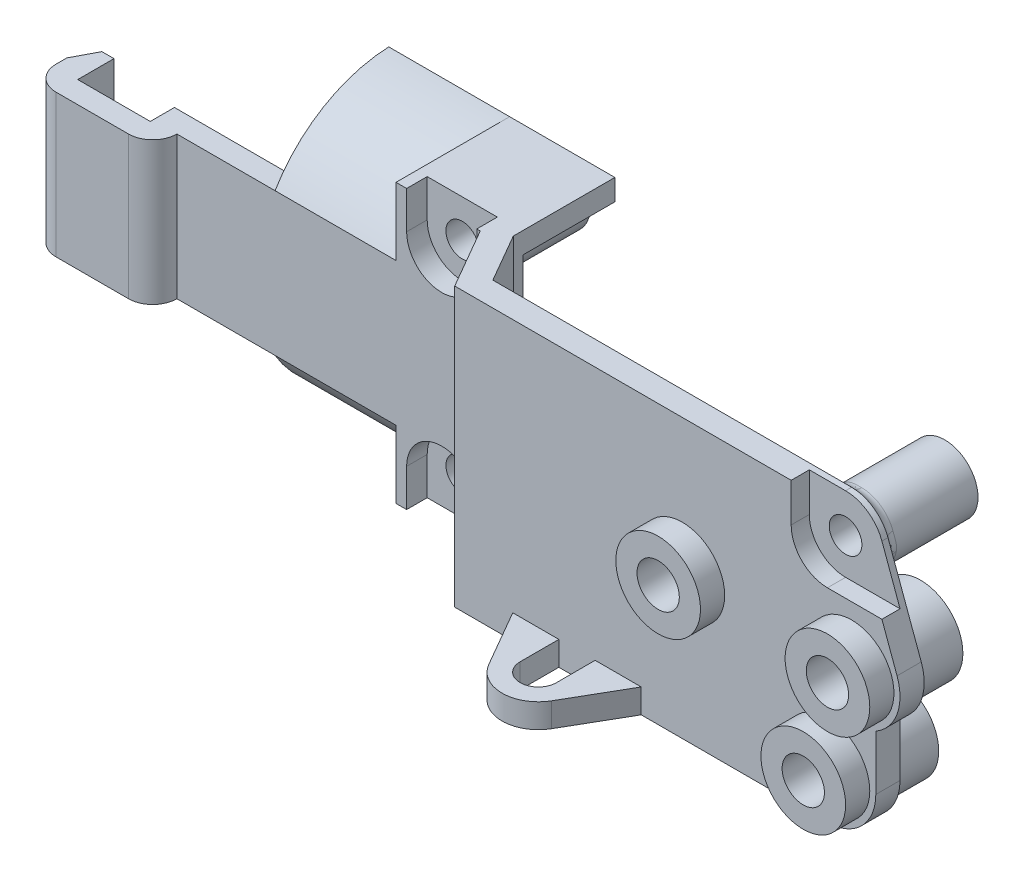
SolidWorks part; units mm, degrees
ref_plane "Front Plane" through (0, 0, 0) normal (0, 0, 1) x (1, 0, 0)
ref_plane "Top Plane" through (0, 0, 0) normal (0, 1, 0) x (1, 0, 0)
ref_plane "Right Plane" through (0, 0, 0) normal (1, 0, 0) x (0, 0, -1)
sketch "Sketch1" plane through (0, 0, 0) normal (0, 0, 1) x (1, 0, 0)
  line L0 (-4.567, -11.8) -> (25.103, -11.8)
  line L1 (29.103, -7.8) -> (29.103, -3.2641)
  line L2 (28.1084, 9.0988) -> (30.8598, 1.5735)
  line L3 (25.103, 11.2) -> (-4.567, 11.2)
  line L4 (29.103, -7.8) -> (29.103, -3.2641) construction
  line L9 (999.5524, 0.2) -> (-4.567, 0.2) construction
  line L10 (-4.567, 11.2) -> (-4.567, -11.8)
  arc A0 (29.103, -3.2641) -> (30.8598, 1.5735) centre (27.103, 0.2) ccw
  circle A2 centre (-0.897, 0.2) radius 1.5
  circle A3 centre (13.103, 0.2) radius 1.75
  circle A4 centre (27.103, 0.2) radius 1.75
  circle A5 centre (25.103, -7.8) radius 1.75
  arc A6 (25.103, -11.8) -> (29.103, -7.8) centre (25.103, -7.8) ccw
  circle A7 centre (25.103, 8) radius 1.35
  arc A9 (25.103, 11.2) -> (28.1084, 9.0988) centre (25.103, 8) cw
  circle A12 centre (-0.897, 0.2) radius 1.5 construction
  point P0 (31.103, 0.2)
  dimension "D9" = 3.5
  dimension "D10" = 3.5
  dimension "D11" = 3
  dimension "D12" = 3.5
  dimension "D13" = 2.7
  dimension "D14" = 4
  dimension "D15" = 3.2
  dimension "D19" = 4
  dimension "D3" = 35.67
  dimension "D4" = 14
  dimension "D7" = 12
  dimension "D8" = 2
  dimension "D18" = 23
  dimension "D20" = 8
  dimension "D21" = 7.8
extrude "Boss-Extrude1" add sketch "Sketch1" along normal blind 2 contours L10 L0 A6 L1 A0 L2 A9 L3 | A3 | A7 | A4 | A5
ref_plane "Plane1" through (0, -0.3, 0) normal (0, 1, 0) x (-1, 0, 0)
sketch "Sketch4" plane through (0, 0, 0) normal (0, 0, 1) x (1, 0, 0)
  circle A0 centre (27.103, 0.2) radius 3.5
  circle A1 centre (27.103, 0.2) radius 1.75 construction
  circle A2 centre (27.103, 0.2) radius 1.75
  circle A3 centre (25.103, -7.8) radius 1.75 construction
  circle A4 centre (25.103, -7.8) radius 1.75
  circle A5 centre (25.103, -7.8) radius 3.5
  dimension "D1" = 7
extrude "Boss-Extrude3" add sketch "Sketch4" against normal offset from surface (3.7 mm away) 3.7 up to face at (28.853, 0.2, 0) offset beyond the face yes
sketch "Sketch3" plane through (0, 0, 2) normal (0, 0, -1) x (-1, 0, 0)
  circle A0 centre (-25.103, -7.8) radius 3.5
  circle A1 centre (-25.103, -7.8) radius 1.75 construction
  circle A2 centre (-25.103, -7.8) radius 1.75
  circle A3 centre (-27.103, 0.2) radius 1.75 construction
  circle A4 centre (-13.103, 0.2) radius 1.75 construction
  circle A5 centre (-27.103, 0.2) radius 1.75
  circle A6 centre (-13.103, 0.2) radius 1.75
  circle A7 centre (-27.103, 0.2) radius 3.5
  circle A8 centre (-13.103, 0.2) radius 3.5
  dimension "D1" = 7
extrude "Boss-Extrude4" add sketch "Sketch3" against normal offset from surface (2 mm away) 7.7 up to face at (30.603, 0.2, -3.7)
sketch "Sketch5" plane through (0, -0.3, 0) normal (0, 1, 0) x (1, 0, 0)
  line L0 (-4.567, -2) -> (-4.567, 0) construction
  line L8 (29.9414, -1) -> (13.8394, -1) construction
  line L17 (25.103, 0) -> (-4.567, 0) construction
  line L18 (25.103, -2) -> (-4.567, -2) construction
  line L19 (-5.7217, -2) -> (-8.6085, 3)
  line L20 (-6.8764, 4) -> (-4.567, 0)
  line L21 (-4.567, 0) -> (-4.567, -2)
  line L22 (-4.567, -2) -> (-5.7217, -2)
  line L23 (-33.697, 3) -> (-8.6085, 3)
  line L24 (-33.697, 1) -> (-33.697, 3)
  line L25 (-43.697, 1) -> (-33.697, 1)
  line L26 (-43.697, 3.9) -> (-43.697, 1)
  line L27 (-42.697, 5.8) -> (-43.697, 3.9)
  line L28 (-41.697, 5.8) -> (-42.697, 5.8)
  line L29 (-41.697, 2.8) -> (-41.697, 5.8)
  line L30 (-35.697, 2.8) -> (-41.697, 2.8)
  line L31 (-35.697, 4.8) -> (-35.697, 2.8)
  line L32 (-6.8764, 4.8) -> (-35.697, 4.8)
  line L33 (-6.8764, 4.8) -> (-6.8764, 4)
  dimension "D1" = 120
  dimension "D2" = 1.8
  dimension "D3" = 1.9
  dimension "D4" = 1
  dimension "D5" = 1.8
  dimension "D6" = 5
  dimension "D7" = 2
  dimension "D8" = 2
  dimension "D9" = 1
  dimension "D10" = 2
  dimension "D11" = 2
  dimension "D12" = 8
  dimension "D13" = 1
  dimension "D14" = 34.8
extrude "Boss-Extrude5" add sketch "Sketch5" along normal mid plane 11.8
fillet "Fillet1" radius 2 2 edges at (-43.697, -0.3, -1) (-33.697, -0.3, -1)
sketch "Sketch6" plane through (0, 0, 0) normal (0, 0, 1) x (1, 0, 0)
  circle A0 centre (25.103, 8) radius 1.35 construction
  circle A1 centre (25.103, 8) radius 1.35
  circle A2 centre (25.103, 8) radius 2.75
  dimension "D1" = 5.5
extrude "Boss-Extrude6" add sketch "Sketch6" against normal blind 7.7
sketch "Sketch8" plane through (0, 0, 0) normal (0, 0, 1) x (1, 0, 0)
  circle A0 centre (-0.897, 0.2) radius 3
  circle A1 centre (-0.897, 0.2) radius 1.5 construction
  circle A2 centre (-0.897, 0.2) radius 1.5
  dimension "D1" = 6
extrude "Boss-Extrude7" add sketch "Sketch8" against normal blind 2.65
sketch "Sketch9" plane through (0, -0.3, 0) normal (0, -1, 0) x (1, 0, 0)
  line L5 (-8.6085, -3) -> (-5.7217, 2) construction
  line L6 (-4.567, 0) -> (-6.8764, -4) construction
  line L7 (-6.8764, -4.8) -> (-35.697, -4.8) construction
  line L8 (-6.8764, -4) -> (-6.8764, -4.8) construction
  line L13 (-1.123, 1) -> (4.8741, 1) construction
  line L14 (-4.567, 0) -> (25.103, 0) construction
  line L15 (-4.567, 2) -> (25.103, 2) construction
  line L16 (-8.6085, -4.8) -> (-6.8764, -4.8)
  line L17 (-8.6085, -3) -> (-8.6085, -4.8)
  line L18 (-6.8764, -4.8) -> (-6.8764, -4)
  line L19 (-4.567, 0) -> (-4.567, 2)
  line L20 (-6.8764, -4) -> (-4.567, 0)
  line L21 (-4.567, 2) -> (-5.7217, 2)
  line L22 (-5.7217, 2) -> (-8.6085, -3)
extrude "Boss-Extrude10" add sketch "Sketch9" along normal mid plane 23
sketch "Sketch10" plane through (0, 0, -3) normal (0, 0, -1) x (-1, 0, 0)
  line L0 (25.5764, -11.8) -> (6.8764, -11.8)
  line L1 (6.8764, -11.8) -> (6.8764, -10.05)
  line L2 (6.8764, -10.05) -> (9.2304, -10.05)
  line L3 (12.9925, -6.0579) -> (14.597, -4.6025)
  line L4 (14.597, -4.6025) -> (14.597, 4.0025)
  line L5 (16.397, 4.8) -> (16.397, -5.4)
  line L6 (16.397, -5.4) -> (14.3251, -7.2792)
  line L7 (14.0708, -10.5) -> (25.5764, -10.5)
  line L8 (25.5764, -10.5) -> (25.5764, -11.8)
  line L9 (25.5764, 9.9) -> (25.5764, 11.2)
  line L10 (14.0708, 9.9) -> (25.5764, 9.9)
  line L11 (16.397, 4.8) -> (14.3251, 6.6792)
  line L12 (-8.6455, -0.3) -> (-5.3863, -0.3) construction
  line L13 (-25.103, 11.2) -> (5.7217, 11.2) construction
  line L14 (12.9925, 5.4579) -> (14.597, 4.0025)
  line L15 (6.8764, 9.45) -> (9.2304, 9.45)
  line L16 (6.8764, 11.2) -> (6.8764, 9.45)
  line L17 (25.5764, 11.2) -> (6.8764, 11.2)
  line L18 (6.8764, 11.2) -> (6.8764, -11.8) construction
  line L19 (6.8764, 11.2) -> (6.8764, -11.8) construction
  line L22 (5.7217, -11.8) -> (-25.103, -11.8) construction
  line L25 (16.397, 4.8) -> (16.397, 2.7) construction
  line L26 (-25.103, 11.2) -> (4.567, 11.2) construction
  arc A0 (9.2304, -10.05) -> (12.9925, -6.0579) centre (11.797, -8.7) cw
  arc A1 (14.3251, -7.2792) -> (14.0708, -10.5) centre (11.797, -8.7) cw
  arc A2 (14.3251, 6.6792) -> (14.0708, 9.9) centre (11.797, 8.1) ccw
  arc A3 (9.2304, 9.45) -> (12.9925, 5.4579) centre (11.797, 8.1) ccw
  circle A4 centre (11.797, 8.1) radius 1.35
  circle A5 centre (11.797, -8.7) radius 1.35
  dimension "D1" = 2.9
  dimension "D14" = 2.7
  dimension "D11" = 10.9
  dimension "D2" = 1.3
  dimension "D3" = 1.8
  dimension "D4" = 18.7
  dimension "D5" = 1.8
  dimension "D6" = 10.2
  dimension "D7" = 1.3
  dimension "D8" = 1.75
  dimension "D9" = 3.1
  dimension "D10" = 3.1
  dimension "D12" = 1.8
extrude "Boss-Extrude11" add sketch "Sketch10" along normal offset from surface (9.4 mm away) 9.4 up to face at (-21.1527, -0.3, -3)
sketch "Sketch11" plane through (0, 0, -3) normal (0, 0, -1) x (-1, 0, 0)
  line L0 (25.5764, 11.2) -> (8.6085, 11.2) construction
  line L1 (8.6085, -11.8) -> (17.0924, -11.8)
  line L2 (8.6085, -11.8) -> (8.6085, 11.2)
  line L3 (8.6085, 11.2) -> (17.0924, 11.2)
  line L4 (17.0924, -11.8) -> (17.0924, 11.2)
  line L6 (8.6085, 5.6) -> (8.6085, -6.2) construction
  line L7 (8.6085, -11.8) -> (25.5764, -11.8) construction
  circle A0 centre (11.797, 8.1) radius 1.35 construction
  circle A1 centre (11.797, -8.7) radius 1.35 construction
  circle A2 centre (11.797, 8.1) radius 1.35
  circle A3 centre (11.797, -8.7) radius 1.35
extrude "Boss-Extrude12" add sketch "Sketch11" along normal up to surface (1.8 mm away) up to face at (-10.3321, -0.3, -4.8)
sketch "Sketch13" plane through (0, 0, 2) normal (0, 0, -1) x (-1, 0, 0)
  line L0 (-29.607, 5) -> (-25.103, 5)
  line L1 (-28.1084, 9.0988) -> (-30.8598, 1.5735) construction
  line L2 (-22.103, 8) -> (-22.103, 11.2)
  line L3 (-25.103, 11.2) -> (4.567, 11.2) construction
  line L4 (-28.1084, 9.0988) -> (-29.607, 5)
  line L5 (-25.103, 11.2) -> (-22.103, 11.2)
  arc A0 (-25.103, 5) -> (-22.103, 8) centre (-25.103, 8) ccw
  circle A1 centre (-25.103, 8) radius 1.35 construction
  arc A2 (-25.103, 11.2) -> (-28.1084, 9.0988) centre (-25.103, 8) ccw construction
  arc A3 (-25.103, 11.2) -> (-28.1084, 9.0988) centre (-25.103, 8) ccw
  dimension "D1" = 3
extrude "Cut-Extrude3" cut sketch "Sketch13" along normal blind 1.5
fillet "Fillet2" radius 1 1 edges at (27.853, 8, 0)
sketch "Sketch14" plane through (-25.5764, 0, 0) normal (-1, 0, 0) x (0, 0, 1)
  line L1 (-12.4, 3.4085) -> (-12.4, -5.8) construction
  line L4 (-12.4, -10.5) -> (-12.4, -11.8)
  line L5 (-4.8, -6.2) -> (-3, -6.2)
  line L6 (-12.4, -5.4) -> (-12.4, 4.8) construction
  line L7 (-4.8, -6.2) -> (-2.8, -6.2) construction
  line L8 (-12.4, -10.5) -> (-3, -10.5) construction
  line L9 (-12.4, -11.8) -> (-3, -11.8) construction
  arc A0 (-12.4, -10.5) -> (-4.8, -6.2) centre (-13.0302, -0.5199) ccw
  arc A1 (-12.4, -11.8) -> (-3, -6.2) centre (-12.8771, -0.3099) ccw
  dimension "D1" = 10
  dimension "D2" = 11.5
sketch "Sketch23" plane through (-25.5764, 0, -25.5764) normal (1, 0, 0) x (0, 0, -1)
  line L1 (-14.9764, -1001.8209) -> (-14.9764, 48998.1791) construction
  line L3 (-13.1764, 9.9) -> (-13.1764, 11.2)
  line L4 (-20.7764, 5.6) -> (-22.5764, 5.6)
  arc A0 (-13.1764, 9.9) -> (-20.7764, 5.6) centre (-12.5462, -0.0801) ccw
  arc A1 (-13.1764, 11.2) -> (-22.5764, 5.6) centre (-12.6993, -0.2901) ccw
  dimension "D1" = 10
  dimension "D2" = 11.5
extrude "Boss-Extrude20" add sketch "Sketch14" against normal up to body
extrude "Boss-Extrude19" add sketch "Sketch23" along normal up to body
sketch "Sketch12" plane through (0, 0, -3) normal (0, 0, -1) x (-1, 0, 0)
  line L0 (8.897, -11.8) -> (8.897, -8.7)
  line L1 (8.6085, -11.8) -> (25.5764, -11.8) construction
  line L2 (14.697, -8.7) -> (14.697, -11.8)
  line L3 (14.697, -11.8) -> (8.897, -11.8)
  arc A0 (8.897, -8.7) -> (14.697, -8.7) centre (11.797, -8.7) cw
  arc A1 (12.9925, -6.0579) -> (9.2304, -10.05) centre (11.797, -8.7) ccw construction
extrude "Cut-Extrude1" cut sketch "Sketch12" along normal blind 1.7
mirror "Mirror1" about plane through (0, -0.3, 0) normal (0, 1, 0) of "Cut-Extrude1"
sketch "Sketch17" plane through (0, 0, -3) normal (0, 0, -1) x (-1, 0, 0)
  line L0 (15.197, 11.2) -> (15.197, 6.7766)
  line L1 (25.5764, 11.2) -> (14.697, 11.2) construction
  line L2 (15.197, 6.7766) -> (16.197, 6.7766)
  line L3 (16.197, 6.7766) -> (16.197, 11.2)
  line L4 (15.197, 11.2) -> (16.197, 11.2)
  line L5 (14.697, 11.2) -> (14.697, 8.1) construction
  dimension "D1" = 0.5
  dimension "D2" = 1
extrude "Boss-Extrude21" add sketch "Sketch17" along normal up to next
sketch "Sketch18" plane through (-25.5764, 0, 0) normal (-1, 0, 0) x (0, 0, 1)
  line L0 (-12.4, 11.2) -> (-3, 11.2) construction
  line L3 (-12.4, 11.2) -> (-3, 11.2)
  line L4 (-3, 11.2) -> (-3, 5.6)
  arc A0 (-12.4, 11.2) -> (-3, 5.6) centre (-12.8771, -0.2901) cw
  arc A1 (-3, 5.6) -> (-7.5468, 9.9) centre (-12.8771, -0.2901) ccw construction
extrude "Cut-Extrude5" cut sketch "Sketch18" against normal blind 10
sketch "Sketch19" plane through (0, 0, -3) normal (0, 0, -1) x (-1, 0, 0)
  line L0 (14.697, -11.8) -> (25.5764, -11.8) construction
  line L1 (15.197, -11.8) -> (16.697, -11.8)
  line L2 (15.197, -11.8) -> (15.197, -5.8923)
  line L3 (15.197, -5.8923) -> (16.697, -5.8923)
  line L4 (16.697, -11.8) -> (16.697, -5.8923)
  line L6 (14.697, -11.8) -> (14.697, -8.7) construction
  point P6 (14.697, -10.25)
  dimension "D1" = 0.5
  dimension "D2" = 1.5
extrude "Boss-Extrude22" add sketch "Sketch19" along normal up to surface (9.4 mm away) up to face at (-19.0676, -8.3662, -4.9025)
mirror "Mirror2" about plane through (0, -0.3, 0) normal (0, 1, 0) of "Cut-Extrude5"
sketch "Sketch21" plane through (-16.397, 0, 0) normal (-1, 0, 0) x (0, 0, 1)
  line L0 (-12.4, 4.8) -> (-12.4, -5.4) construction
  circle A0 centre (-12.4, -0.3) radius 3
  dimension "D1" = 6
extrude "Cut-Extrude7" cut sketch "Sketch21" against normal up to next
sketch "Sketch22" plane through (0, -11.8, 0) normal (0, -1, 0) x (1, 0, 0)
  line L8 (18.5687, 1) -> (14.3563, 1) construction
  line L9 (-5.7217, 2) -> (25.103, 2) construction
  line L10 (-4.567, 0) -> (25.103, 0) construction
  line L11 (5.8915, 2) -> (5.8915, 5.2)
  line L12 (5.8915, 2) -> (9.7032, 2)
  line L13 (2.8915, 5.2) -> (2.8915, 2)
  line L14 (-0.9201, 2) -> (2.8915, 2)
  line L15 (6.9896, 6.7) -> (9.7032, 2)
  line L16 (-0.9201, 2) -> (1.7935, 6.7)
  arc A2 (2.8915, 5.2) -> (5.8915, 5.2) centre (4.3915, 5.2) cw
  arc A3 (1.7935, 6.7) -> (6.9896, 6.7) centre (4.3915, 5.2) cw
  point P39 (4.3915, 8.2)
  dimension "D2" = 1.5
  dimension "D3" = 3
  dimension "D5" = 120
  dimension "D1" = 13
  dimension "D4" = 120
  dimension "D6" = 6.2
extrude "Boss-Extrude17" add sketch "Sketch22" against normal blind 2
